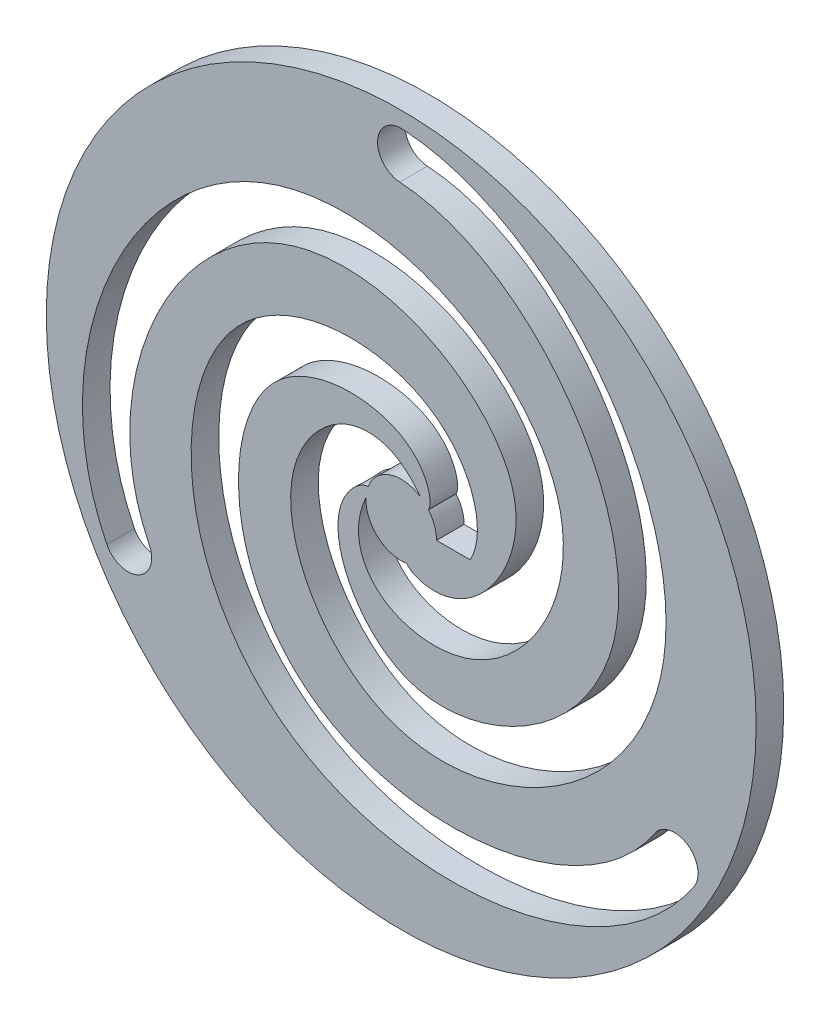
SolidWorks part; units mm, degrees
ref_plane "Alzado" through (0, 0, 0) normal (0, 0, 1) x (1, 0, 0)
ref_plane "Planta" through (0, 0, 0) normal (0, 1, 0) x (1, 0, 0)
ref_plane "Vista lateral" through (0, 0, 0) normal (1, 0, 0) x (0, 0, -1)
sketch "Croquis1" plane through (0, 0, 0) normal (0, 0, 1) x (1, 0, 0)
  circle A0 centre (0, 0) radius 45
  dimension "D1" = 90
extrude "Disk" add sketch "Croquis1" along normal blind 3.5
sketch "Croquis6" plane through (0, 0, 3.5) normal (0, 0, 1) x (1, 0, 0)
  line L6 (0, 0) -> (0, 40) construction
  line L7 (0, 0) -> (30, 0)
  line L8 (0, 0) -> (0, -20) construction
  line L9 (0, 0) -> (-10, 0) construction
  line L10 (0, 40) -> (30, 0) construction
  line L11 (30, 0) -> (0, -20) construction
  line L12 (0, -20) -> (-10, 0) construction
  line L13 (0, 0) -> (0, 2) construction
  line L14 (-10, 0) -> (0, 2) construction
  line L15 (15, 20) -> (31.3618, 32.2713) construction
  line L16 (15, -10) -> (30.4326, -33.149) construction
  line L17 (-5, -10) -> (-36.7995, -25.8997) construction
  line L18 (-5, 1) -> (-13.3922, 42.961) construction
  circle A0 centre (0, 40) radius 3
  circle A1 centre (34.641, -20) radius 3
  circle A2 centre (-34.641, -20) radius 3
  circle A3 centre (0, 0) radius 45 construction
  circle A4 centre (0, 0) radius 4.4768
  spline S0 degree 3 poles (0, 40) (18.1548, 38.8882) (39.4406, 9.9044) (20.8408, -18.0323) (1.4904, -23.4335) (-10.2193, -12.7712) (-12.6266, 0.7699) (-3.6122, 6.9847) (0, 2) knots 0 0 0 0 0.418034 0.568629 0.719224 0.812318 0.905413 1 1 1 1
  spline S1 degree 3 poles (34.641, -20) (24.6007, -35.1666) (-11.1429, -39.1087) (-26.0369, -9.0325) (-21.0392, 10.426) (-5.9505, 15.2358) (6.98, 10.55) (7.855, -0.3641) (1.7321, -1) knots 0 0 0 0 0.418034 0.568629 0.719224 0.812318 0.905413 1 1 1 1
  spline S2 degree 3 poles (-34.641, -20) (-42.7555, -3.7216) (-28.2977, 29.2044) (5.196, 27.0649) (19.5488, 13.0075) (16.1699, -2.4646) (5.6465, -11.3199) (-4.2428, -6.6206) (-1.7321, -1) knots 0 0 0 0 0.418034 0.568629 0.719224 0.812318 0.905413 1 1 1 1
  spline S3 degree 1 poles (-31.9561, -18.6616) (1.0071, -2.2236) knots 0 0 1 1 construction
  spline S4 degree 3 poles (-31.9561, -18.6616) (-33.0253, -16.5168) (-34.4316, -11.9133) (-34.5493, -4.3217) (-32.7936, 3.3815) (-29.38, 10.6223) (-24.5764, 16.8233) (-18.69, 21.4602) (-12.0607, 24.0638) (-4.7375, 24.4388) (2.5751, 22.5783) (9.3189, 18.3916) (13.1431, 13.5807) (14.5066, 9.5382) (14.6556, 6.3113) (13.9563, 2.9304) (12.4432, -0.3118) (10.2149, -3.145) (8.0013, -4.7549) (6.1409, -5.4747) (4.7096, -5.7267) (3.1599, -5.6675) (1.7928, -5.298) (0.934, -4.7454) (0.7027, -4.4016) (0.6062, -4.1005) (0.5755, -3.7315) (0.6492, -3.2251) (0.8078, -2.7024) (0.9393, -2.3753) (1.0071, -2.2236) knots 0 0 0 0 0.0625 0.125 0.1875 0.25 0.3125 0.375 0.4375 0.5 0.5625 0.625 0.6875 0.71875 0.75 0.78125 0.8125 0.84375 0.875 0.890625 0.90625 0.921875 0.9375 0.953125 0.96875 0.976562 0.984375 0.992188 0.996094 1 1 1 1
  spline S5 degree 1 poles (-0.1834, 37.0056) (-2.4292, 0.2396) knots 0 0 1 1 construction
  spline S6 degree 3 poles (-0.1834, 37.0056) (2.2087, 36.8591) (6.8986, 35.7753) (13.5319, 32.0814) (19.3252, 26.7094) (23.8892, 20.1327) (26.8575, 12.8721) (27.93, 5.4559) (26.8702, -1.5871) (23.5334, -8.1166) (18.2658, -13.5192) (11.2682, -17.2662) (5.1896, -18.1726) (1.007, -17.3322) (-1.8621, -15.8478) (-4.4403, -13.5517) (-6.4917, -10.6202) (-7.8311, -7.2739) (-8.1185, -4.5518) (-7.8117, -2.5808) (-7.3142, -1.2153) (-6.4882, 0.0972) (-5.4846, 1.0964) (-4.5766, 1.5639) (-4.1633, 1.5922) (-3.8542, 1.5252) (-3.5193, 1.3674) (-3.1177, 1.0503) (-2.7442, 0.6516) (-2.5267, 0.3742) (-2.4292, 0.2396) knots 0 0 0 0 0.0625 0.125 0.1875 0.25 0.3125 0.375 0.4375 0.5 0.5625 0.625 0.6875 0.71875 0.75 0.78125 0.8125 0.84375 0.875 0.890625 0.90625 0.921875 0.9375 0.953125 0.96875 0.976562 0.984375 0.992188 0.996094 1 1 1 1
  spline S7 degree 1 poles (32.1395, -18.344) (1.4221, 1.984) knots 0 0 1 1 construction
  spline S8 degree 3 poles (32.1395, -18.344) (30.8166, -20.3423) (27.5331, -23.862) (21.0174, -27.7597) (13.4684, -30.0908) (5.4908, -30.755) (-2.2812, -29.6954) (-9.24, -26.9161) (-14.8095, -22.4767) (-18.7958, -16.3222) (-20.8409, -9.059) (-20.5871, -1.1255) (-18.3328, 4.5919) (-15.5136, 7.794) (-12.7936, 9.5365) (-9.5159, 10.6213) (-5.9515, 10.932) (-2.3838, 10.4188) (0.1173, 9.3068) (1.6708, 8.0555) (2.6046, 6.942) (3.3283, 5.5703) (3.6918, 4.2017) (3.6427, 3.1815) (3.4605, 2.8094) (3.248, 2.5752) (2.9438, 2.3641) (2.4684, 2.1748) (1.9364, 2.0508) (1.5874, 2.0011) (1.4221, 1.984) knots 0 0 0 0 0.0625 0.125 0.1875 0.25 0.3125 0.375 0.4375 0.5 0.5625 0.625 0.6875 0.71875 0.75 0.78125 0.8125 0.84375 0.875 0.890625 0.90625 0.921875 0.9375 0.953125 0.96875 0.976562 0.984375 0.992188 0.996094 1 1 1 1
  spline S9 degree 1 poles (-37.3259, -21.3384) (-4.4712, 0.2236) knots 0 0 1 1 construction
  spline S10 degree 3 poles (-37.3259, -21.3384) (-38.002, -19.982) (-39.1319, -17.1437) (-40.4687, -11.26) (-40.566, -3.6404) (-38.5036, 5.3674) (-34.5462, 13.7634) (-28.9168, 21.0504) (-22.979, 25.7515) (-17.572, 28.3785) (-11.7673, 30.114) (-4.119, 30.501) (4.9814, 28.1719) (11.8965, 23.8905) (16.3385, 19.2765) (18.9156, 15.2541) (20.4836, 10.6642) (20.6971, 5.7715) (19.6912, 1.0004) (17.6032, -3.4705) (14.5042, -7.4403) (11.0573, -10.0047) (7.7884, -11.2874) (5.1012, -11.7578) (2.3087, -11.6526) (-0.4327, -10.9434) (-3.0073, -9.4723) (-4.7037, -7.3177) (-5.3665, -5.1167) (-5.4596, -3.3566) (-5.2142, -1.8651) (-4.8466, -0.6764) (-4.6026, -0.0707) (-4.4712, 0.2236) knots 0 0 0 0 0.03125 0.0625 0.125 0.1875 0.25 0.3125 0.375 0.40625 0.4375 0.5 0.5625 0.625 0.65625 0.6875 0.71875 0.75 0.78125 0.8125 0.84375 0.875 0.890625 0.90625 0.921875 0.9375 0.953125 0.96875 0.976562 0.984375 0.992188 0.996094 1 1 1 1
  spline S11 degree 1 poles (0.1834, 42.9944) (2.4292, 3.7604) knots 0 0 1 1 construction
  spline S12 degree 3 poles (0.1834, 42.9944) (1.6961, 42.9018) (4.7191, 42.4611) (10.4829, 40.6769) (17.1303, 36.9514) (23.9001, 30.6614) (29.1925, 23.0362) (32.6886, 14.5175) (33.791, 7.0246) (33.3625, 1.0285) (31.9631, -4.8662) (28.4741, -11.6833) (21.9069, -18.4) (14.7416, -22.2479) (8.5247, -23.7878) (3.7526, -24.0084) (-1.0063, -23.0714) (-5.3503, -20.81) (-8.9792, -17.5533) (-11.8072, -13.5095) (-13.6956, -8.8409) (-14.193, -4.5735) (-13.6694, -1.1012) (-12.7332, 1.4612) (-11.2458, 3.8269) (-9.261, 5.8464) (-6.6996, 7.3405) (-3.9854, 7.7324) (-1.7479, 7.2059) (-0.1771, 6.4065) (0.9919, 5.4482) (1.8375, 4.5355) (2.2401, 4.0213) (2.4292, 3.7604) knots 0 0 0 0 0.03125 0.0625 0.125 0.1875 0.25 0.3125 0.375 0.40625 0.4375 0.5 0.5625 0.625 0.65625 0.6875 0.71875 0.75 0.78125 0.8125 0.84375 0.875 0.890625 0.90625 0.921875 0.9375 0.953125 0.96875 0.976562 0.984375 0.992188 0.996094 1 1 1 1
  spline S13 degree 1 poles (37.1425, -21.656) (2.042, -3.984) knots 0 0 1 1 construction
  spline S14 degree 3 poles (37.1425, -21.656) (36.306, -22.9197) (34.4129, -25.3174) (29.9857, -29.4169) (23.4357, -33.311) (14.6035, -36.0288) (5.3536, -36.7995) (-3.7718, -35.5679) (-10.812, -32.7761) (-15.7905, -29.407) (-20.1958, -25.2478) (-24.3551, -18.8177) (-26.8883, -9.7719) (-26.6381, -1.6426) (-24.8632, 4.5113) (-22.6682, 8.7543) (-19.4772, 12.4072) (-15.3469, 15.0385) (-10.712, 16.5529) (-5.796, 16.9801) (-0.8086, 16.2812) (3.1357, 14.5783) (5.881, 12.3887) (7.632, 10.2967) (8.9371, 7.8257) (9.6936, 5.097) (9.7069, 2.1318) (8.6892, -0.4147) (7.1144, -2.0892) (5.6367, -3.0498) (4.2223, -3.5831) (3.0091, -3.8591) (2.3625, -3.9507) (2.042, -3.984) knots 0 0 0 0 0.03125 0.0625 0.125 0.1875 0.25 0.3125 0.375 0.40625 0.4375 0.5 0.5625 0.625 0.65625 0.6875 0.71875 0.75 0.78125 0.8125 0.84375 0.875 0.890625 0.90625 0.921875 0.9375 0.953125 0.96875 0.976562 0.984375 0.992188 0.996094 1 1 1 1
  point P9 (0, 0)
  point P49 (0, 0)
  dimension "D1" = 6
  dimension "D3" = 30
  dimension "D5" = 10
  dimension "D2" = 40
  dimension "D6" = 2
  dimension "D4" = 20
  dimension "D7" = 90
  dimension "D8" = 35
  dimension "D9" = 25
  dimension "D10" = 15
  dimension "D11" = 3
  dimension "D12" = 3
extrude "Cortar-Extruir1" cut sketch "Croquis6" against normal blind 10 contours S10 A2 S2 L7 | A2 S4 L7 S2 | S14 A1 S1 L7 | A1 S8 A4 L7 S1 | S12 A0 S0 A4 | A0 S6 L7 S0 | S10 L7 S2 A4 | L7 S4 A4 S2 | L7 S6 A4 S0 | A0 | A2 | A1 region at (4.9082, 1.7572, 3.5) region at (35.1353, -22.8729, 3.5) region at (-22.0601, -17.4976, 3.5) region at (-17.9189, 27.2453, 3.5) region at (24.4652, -14.4409, 3.5) region at (-17.0296, 22.7305, 3.5) region at (7.0078, -5.1885, 3.5) region at (-3.7103, 3.2909, 3.5) region at (2.1234, 41.9973, 3.5) region at (17.4949, -0.2728, 3.5) region at (-31.8034, -19.332, 3.5) region at (28.4593, 0.5017, 3.5)
